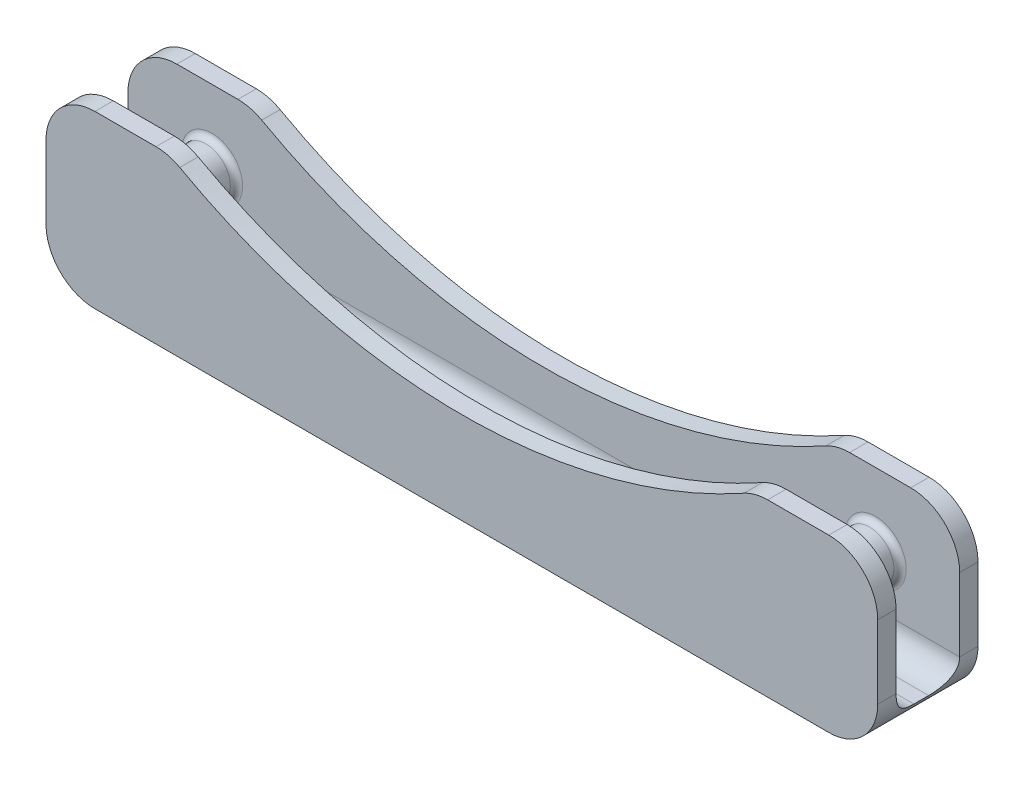
SolidWorks part; units mm, degrees
ref_plane "Front Plane" through (0, 0, 0) normal (0, 0, 1) x (1, 0, 0)
ref_plane "Top Plane" through (0, 0, 0) normal (0, 1, 0) x (1, 0, 0)
ref_plane "Right Plane" through (0, 0, 0) normal (1, 0, 0) x (0, 0, -1)
sketch "Sketch1" plane through (0, 0, 0) normal (0, 0, 1) x (1, 0, 0)
  line L0 (0, 0) -> (0, -110)
  line L1 (-100, -110) -> (100, -110)
  line L2 (-100, -110) -> (-100, -45.8258)
  line L3 (100, -110) -> (100, -45.8258)
  line L4 (-100, -45.8258) -> (-86.3636, -39.5768)
  line L5 (100, -45.8258) -> (86.3636, -39.5768)
  line L6 (86.3636, -39.5768) -> (-86.3636, -39.5768)
  circle A0 centre (0, 0) radius 95
  circle A1 centre (0, 0) radius 110
  arc A2 (-86.3636, -39.5768) -> (86.3636, -39.5768) centre (0, 14.1072) ccw
  point P8 (0, -110)
  dimension "D1" = 190
  dimension "D2" = 220
  dimension "D3" = 200
extrude "Boss-Extrude1" add sketch "Sketch1" along normal blind 3 contours A1 L2 L1 | L4 A1 L0 A0 | L0 A1 L5 A0 | A1 L1 L3
sketch "Sketch2" plane through (0, 0, 3) normal (0, 0, 1) x (1, 0, 0)
  line L0 (0, 0) -> (0, -110)
  line L1 (-100, -110) -> (100, -110) construction
  line L2 (0, 0) -> (-54.25, -93.9638)
  line L3 (100, -110) -> (100, -45.8258) construction
  line L4 (-100, -110) -> (100, -110)
  line L5 (-100, -110) -> (-100, -106)
  line L6 (-100, -106) -> (100, -106)
  line L7 (100, -110) -> (100, -106)
  circle A0 centre (-54.25, -93.9638) radius 4
  circle A1 centre (54.25, -93.9638) radius 4
  dimension "D2" = 8
  dimension "D1" = 108.5
  dimension "D3" = 4
extrude "Boss-Extrude2" add sketch "Sketch2" along normal blind 5.2
sketch "Sketch4" plane through (0, 0, 3) normal (0, 0, 1) x (1, 0, 0)
  line L0 (-100, -106) -> (-100, -45.8258) construction
  line L1 (-100, -82.0451) -> (100.2566, -82.0451)
  line L2 (-100, -82.0451) -> (-100, -36.224)
  line L3 (-100, -36.224) -> (100.2566, -36.224)
  line L4 (100.2566, -82.0451) -> (100.2566, -36.224)
extrude "Cut-Extrude3" cut sketch "Sketch4" against normal through all both and the other way through all
sketch "Sketch5" plane through (0, 0, 0) normal (0, 0, -1) x (-1, 0, 0)
  line L0 (100, -110) -> (-100, -110) construction
  line L1 (-100, -82.0451) -> (-68, -82.0451)
  line L2 (-100, -82.0451) -> (-100, -110)
  line L3 (-100, -110) -> (-68, -110)
  line L4 (-68, -82.0451) -> (-68, -110)
  line L6 (100, -82.0451) -> (68, -82.0451)
  line L7 (100, -82.0451) -> (100, -110)
  line L8 (100, -110) -> (68, -110)
  line L9 (68, -82.0451) -> (68, -110)
  dimension "D1" = 32
  dimension "D2" = 32
extrude "Cut-Extrude4" cut sketch "Sketch5" against normal through all both and the other way through all
fillet "Fillet1" radius 1 2 edges at (58.25, -93.9638, 3) (-50.25, -93.9638, 3)
fillet "Fillet2" radius 4 1 edges at (0, -106, 3)
mirror "Mirror1" about plane through (0, 0, 8.2) normal (0, 0, 1) of bodies 105
fillet "Fillet3" radius 8 12 edges at (-68, -110, 8.2) (-68, -106, 8.2) (68, -106, 8.2) (68, -104.8284, 4.1716) (-68, -104.8284, 4.1716) (-68, -82.0451, 14.9) (68, -82.0451, 14.9) (-68, -104.8284, 12.2284) (68, -104.8284, 12.2284) (-68, -82.0451, 1.5) (68, -82.0451, 1.5) (68, -110, 8.2)
fillet "Fillet4" radius 8 4 edges at (-47.8916, -82.0451, 14.9) (47.8916, -82.0451, 14.9) (-47.8916, -82.0451, 1.5) (47.8916, -82.0451, 1.5)
